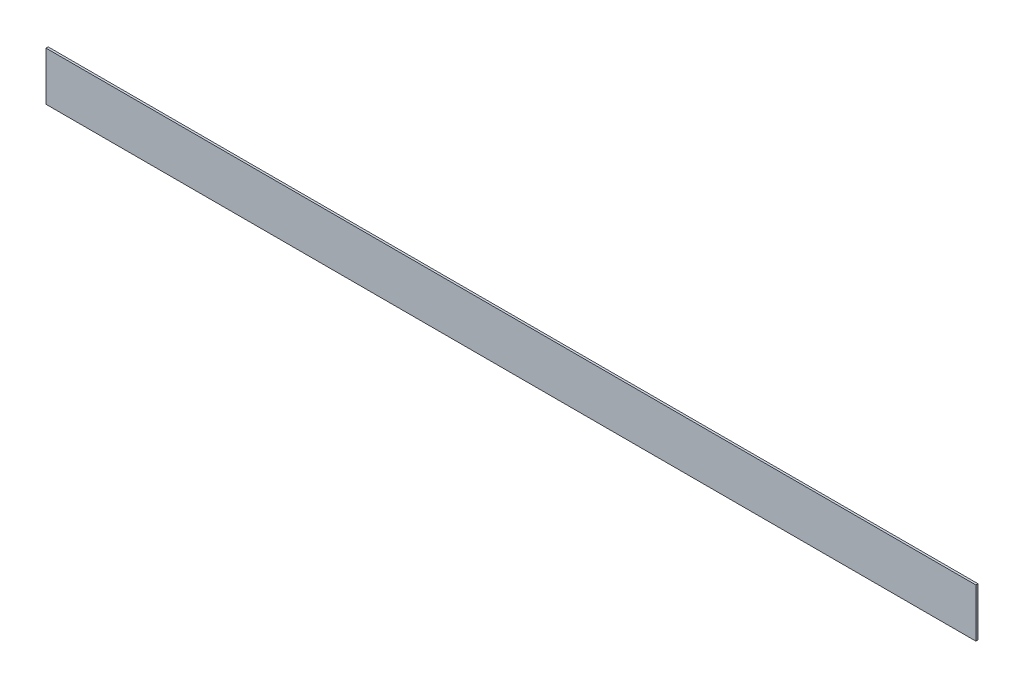
SolidWorks part; units mm, degrees
ref_plane "Ön Düzlem" through (0, 0, 0) normal (0, 0, 1) x (1, 0, 0)
ref_plane "Üst Düzlem" through (0, 0, 0) normal (0, 1, 0) x (1, 0, 0)
ref_plane "Sağ Düzlem" through (0, 0, 0) normal (1, 0, 0) x (0, 0, -1)
sketch "Çizim1" plane through (0, 0, 0) normal (0, 0, 1) x (1, 0, 0)
  line L1 (0, 0) -> (1720, 0)
  line L2 (0, 0) -> (0, -90)
  line L3 (0, -90) -> (1720, -90)
  line L4 (1720, 0) -> (1720, -90)
  dimension "D1" = 1720
  dimension "D2" = 90
base flange "Taban-Flanş1" sketch "Çizim1" thickness 4 reverse thickness direction no parameters "D1"=5
sketch "Büküm-Çizgileri1" [suppressed] plane through (0, 0, 0) normal (0, 1, 0) x (1, 0, 0)
sketch "Sınırlandırma-Kutusu1" [suppressed] plane through (0, 0, 0) normal (0, 1, 0) x (1, 0, 0)
sheet metal parameters "Sac-Levha1" thickness 4 parameters "D1"=5
flat pattern "Düz-Çoğaltma1" [suppressed]
sketch "Büküm-Çizgileri2" plane through (0, 0, 0) normal (0, 1, 0) x (1, 0, 0)
sketch3d "Sınırlandırma-Kutusu2" [suppressed]
  line L0 (0, -90, 0) -> (-1720, -90, 0) construction
  line L1 (0, 0, 0) -> (-1720, 0, 0) construction
  line L2 (0, -90, 0) -> (0, 0, 0) construction
  line L3 (-1720, -90, 0) -> (-1720, 0, 0) construction
